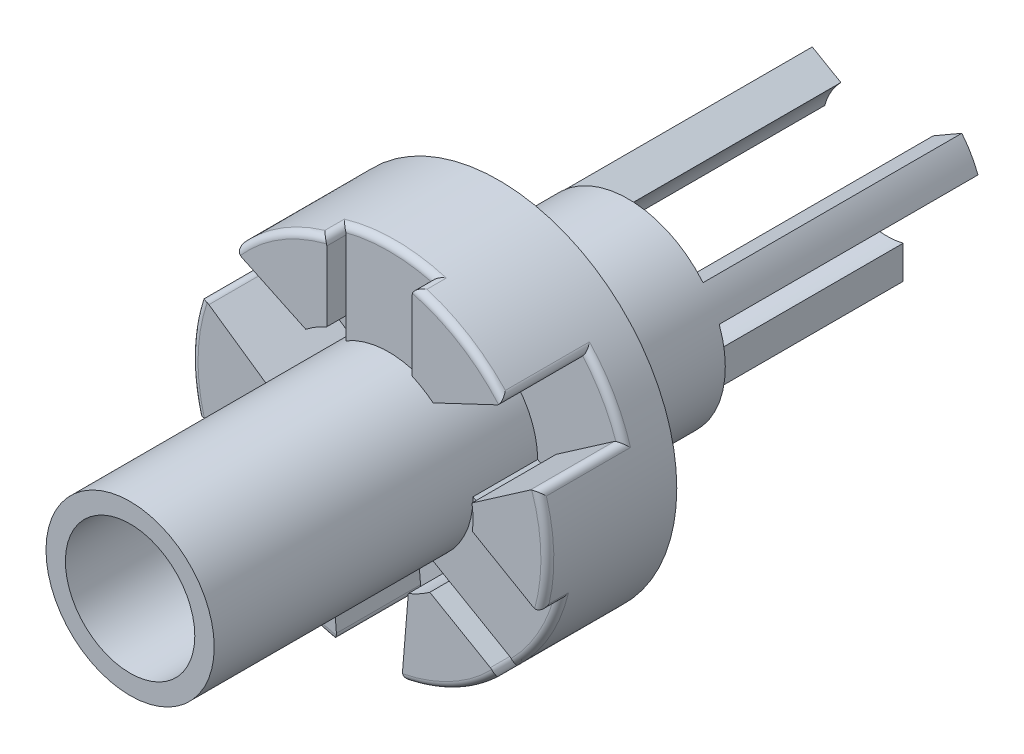
SolidWorks part; units mm, degrees
material "ABS PC"
ref_plane "Front Plane" through (0, 0, 0) normal (0, 0, 1) x (1, 0, 0)
ref_plane "Top Plane" through (0, 0, 0) normal (0, 1, 0) x (1, 0, 0)
ref_plane "Right Plane" through (0, 0, 0) normal (1, 0, 0) x (0, 0, -1)
sketch "Sketch1" plane through (0, 0, 0) normal (0, 0, 1) x (1, 0, 0)
  circle A0 centre (0, 0) radius 0.5
  circle A1 centre (0, 0) radius 0.75
  dimension "D1" = 1
  dimension "D2" = 1.5
extrude "Boss-Extrude1" add sketch "Sketch1" along normal blind 1
sketch "Sketch2" plane through (0, 0, 1) normal (0, 0, 1) x (1, 0, 0)
  circle A0 centre (0, 0) radius 0.5 construction
  circle A1 centre (0, 0) radius 0.5
  circle A2 centre (0, 0) radius 1.375
  dimension "D1" = 2.75
extrude "Boss-Extrude2" add sketch "Sketch2" along normal blind 0.35
sketch "Sketch3" plane through (0, 0, 1.35) normal (0, 0, 1) x (1, 0, 0)
  circle A1 centre (0, 0) radius 0.5 construction
  circle A2 centre (0, 0) radius 0.5
  circle A3 centre (0, 0) radius 0.65
  dimension "D1" = 1.3
extrude "Boss-Extrude3" add sketch "Sketch3" along normal blind 2.5
sketch "Sketch6" plane through (0, 0, 1.35) normal (0, 0, 1) x (1, 0, 0)
  line L0 (0, 1.375) -> (0, 0) construction
  line L1 (0, 0) -> (-1.1908, -0.6875) construction
  line L2 (-0.33, 0.7288) -> (-0.33, 1.3348)
  line L3 (-0.4923, 0.6306) -> (-1.0459, 0.8925)
  line L4 (-1.321, -0.3816) -> (-0.7961, -0.0786)
  line L5 (0, 0) -> (-1.1908, 0.6875) construction
  line L6 (-0.7923, 0.111) -> (-1.2959, 0.4595)
  line L7 (-1.1908, -0.6875) -> (-0.6928, -0.4)
  line L8 (0, 0.8) -> (0, 1.375)
  line L9 (-0.33, 0.7288) -> (-0.33, 0.56)
  line L10 (-0.7961, -0.0786) -> (-0.65, 0.0058)
  line L11 (0, 0.8) -> (0, 0.65)
  line L12 (-0.6928, -0.4) -> (-0.5629, -0.325)
  circle A0 centre (0, 0) radius 0.8 construction
  circle A1 centre (0, 0) radius 1.375 construction
  circle A2 centre (0, 0) radius 1.375 construction
  circle A3 centre (0, 0) radius 0.65 construction
  circle A4 centre (0, 0) radius 0.65 construction
  arc A5 (-0.6928, -0.4) -> (0, 0.8) centre (0, 0) cw
  arc A6 (-1.1908, -0.6875) -> (0, 1.375) centre (0, 0) cw
  arc A7 (-0.5629, -0.325) -> (-0.65, 0.0058) centre (0, 0) cw
  arc A8 (-0.33, 0.56) -> (0, 0.65) centre (0, 0) cw
  circle M12 centre (0, 0) radius 1.375
  circle M13 centre (0, 0) radius 0.65
  dimension "D1" = 0.8
  dimension "D2" = 0.33
  dimension "D3" = 120
  dimension "D4" = 0.33
  dimension "D5" = 60
  dimension "D6" = 0.5
  dimension "D7" = 0.6
extrude "Boss-Extrude4" add sketch "Sketch6" along normal blind 0.65 separate body contours L4 A5 L6 M12 | L3 A5 L2 M12 region at (-0.5941, 0.967, 1.35) region at (-1.1345, 0.031, 1.35)
extrude "Boss-Extrude5" add sketch "Sketch6<4>" along normal blind 0.5 contours L7 A5 L4 M12 | L2 A5 L8 M12 | A5 L9 L11 M13 | A5 L12 L10 M13 region at (-0.1682, 0.698, 1.35) region at (-0.1664, 1.0689, 1.35) region at (-0.6885, -0.2033, 1.35) region at (-1.0089, -0.3903, 1.35)
sketch "Sketch6<4>" plane through (0, 0, 1.35) normal (0, 0, 1) x (1, 0, 0) same geometry as "Sketch6"
pattern_circular "CirPattern1" count 3 over 360 about axis through (0, 0, 3.85) along (0, 0, 1) of bodies 107 105
combine bodies "Combine1" operation type add bodies to combine 108 103 107 111 110 105 109
fillet "Fillet2" radius 0.05 24 edges at (0.6518, -1.2107, 2) (0.991, -0.9532, 1.925) (1.1908, -0.6875, 1.85) (1.321, -0.3816, 1.925) (1.3744, 0.0409, 2) (1.2959, 0.4595, 1.675) (1.0459, 0.8925, 1.675) (0.7226, 1.1698, 2) (0.33, 1.3348, 1.925) (0, 1.375, 1.85) (-0.33, 1.3348, 1.925) (-0.7226, 1.1698, 2) (-1.0459, 0.8925, 1.675) (-1.1908, 0.6875, 1.35) (-1.2959, 0.4595, 1.675) (-1.3744, 0.0409, 2) (-1.321, -0.3816, 1.925) (-1.1908, -0.6875, 1.85) (-0.991, -0.9532, 1.925) (-0.6518, -1.2107, 2) (-0.25, -1.3521, 1.675) (0, -1.375, 1.35) (0.25, -1.3521, 1.675) (1.1908, 0.6875, 1.35)
sketch "Sketch7" plane through (0, 0, 0) normal (0, 0, -1) x (-1, 0, 0)
  line L0 (0, 0) -> (0, -0.75) construction
  line L1 (0, 0) -> (0.6495, 0.375) construction
  line L2 (0.712, 0.2667) -> (0.587, 0.4833)
  line L3 (-0.125, -0.4841) -> (-0.125, -0.75)
  line L4 (0.125, -0.4841) -> (0.125, -0.75)
  line L5 (0.587, 0.4833) -> (0.3568, 0.3503)
  line L6 (0, 0) -> (-0.6495, 0.375) construction
  line L7 (0.125, -0.75) -> (-0.125, -0.75)
  line L8 (0.712, 0.2667) -> (0.4818, 0.1338)
  line L9 (-0.587, 0.4833) -> (-0.712, 0.2667)
  line L10 (-0.587, 0.4833) -> (-0.3568, 0.3503)
  line L11 (-0.712, 0.2667) -> (-0.4818, 0.1338)
  circle A0 centre (0, 0) radius 0.75 construction
  circle A1 centre (0, 0) radius 0.5 construction
  circle A2 centre (0, 0) radius 0.75 construction
  circle A3 centre (0, 0) radius 0.5
  arc A4 (1.3172, 0.3946) -> (1.0003, 0.9434) centre (0, 0) ccw construction
  arc A5 (1.3172, 0.3946) -> (1.0003, 0.9434) centre (0, 0) ccw construction
  point P0 (0.0616, 0.7578)
  point P9 (1.1908, 0.6875)
  point P14 (0.6495, 0.375)
  point P22 (0, -0.75)
  point P25 (-0.6495, 0.375)
  circle M11 centre (0, 0) radius 0.75
  circle M12 centre (0, 0) radius 0.5
  dimension "D3" = 120
  dimension "D1" = 0.25
  dimension "D2" = 120
extrude "Boss-Extrude6" add sketch "Sketch7" along normal blind 2 contours L11 L10 M11 M12 | L8 L5 M11 M12 | L4 L3 M12 M11 region at (-0.5375, 0.3103, 0) region at (0.5375, 0.3103, 0) region at (0, -0.6206, 0)
